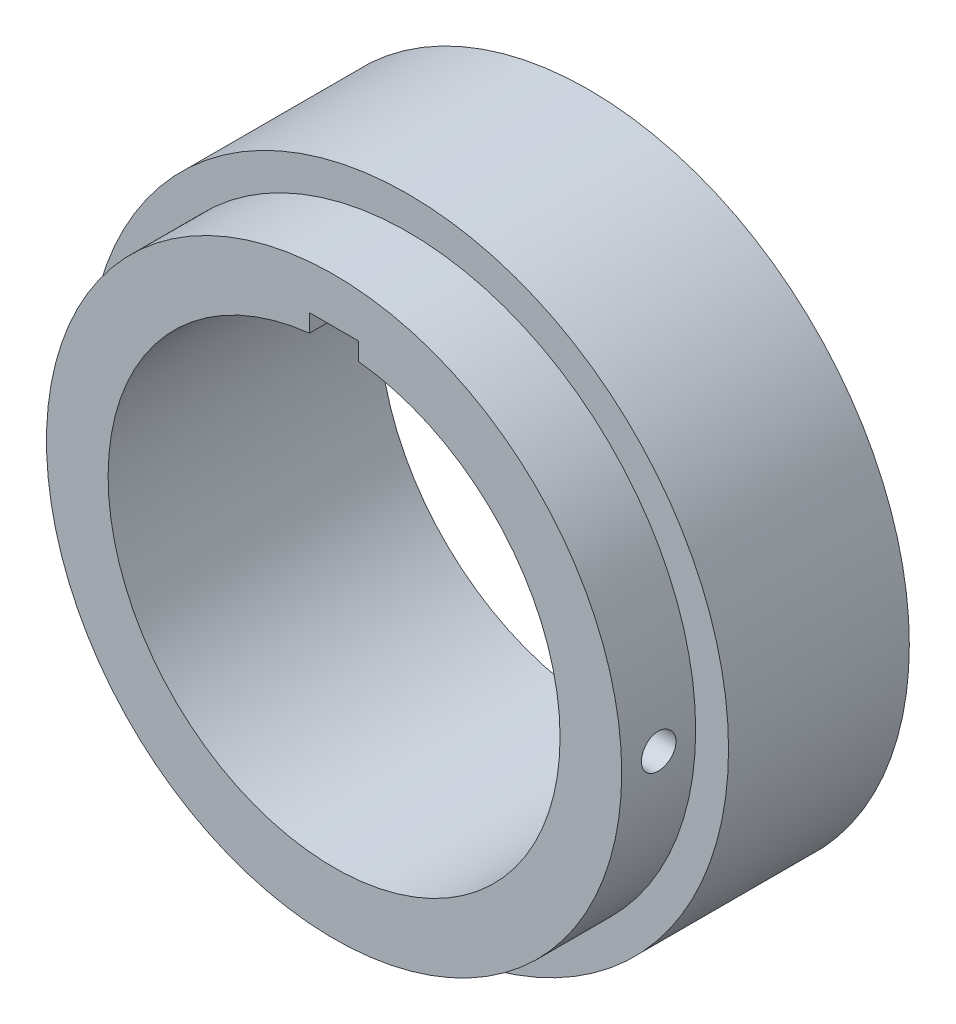
SolidWorks part; units mm, degrees
material "1023 Carbon Steel Sheet (SS)"
ref_plane "Front Plane" through (0, 0, 0) normal (0, 0, 1) x (1, 0, 0)
ref_plane "Top Plane" through (0, 0, 0) normal (0, 1, 0) x (1, 0, 0)
ref_plane "Right Plane" through (0, 0, 0) normal (1, 0, 0) x (0, 0, -1)
sketch "Sketch1" plane through (0, 0, 0) normal (0, 0, 1) x (1, 0, 0)
  circle A0 centre (0, 0) radius 39
  dimension "D1" = 78
extrude "Extrude1" add sketch "Sketch1" along normal blind 22
sketch "Sketch2" plane through (0, 0, 22) normal (0, 0, 1) x (1, 0, 0)
  circle A0 centre (0, 0) radius 35
  dimension "D1" = 70
extrude "Extrude2" add sketch "Sketch2" along normal blind 9
sketch "Sketch4" plane through (0, 0, 0) normal (0, 0, -1) x (-1, 0, 0)
  circle A0 centre (0, 0) radius 37.5
  dimension "D1" = 75
extrude "Extrude4" add sketch "Sketch4" along normal blind 2
sketch "Sketch3" plane through (0, 0, 31) normal (0, 0, 1) x (1, 0, 0)
  line L0 (0, 29.5) -> (0, 0) construction
  line L1 (-3, 29.5) -> (3, 29.5)
  line L2 (-3, 29.5) -> (-3, 27.3359)
  line L4 (3, 29.5) -> (3, 27.3359)
  arc A0 (-3, 27.3359) -> (3, 27.3359) centre (0, 0) ccw
  dimension "D1" = 55
  dimension "D2" = 6
  dimension "D3" = 2
extrude "Extrude3" cut sketch "Sketch3" against normal blind 113
chamfer "Chamfer1" distance 2 angle 45 1 edges at (-37.5, 0, -2)
ref_plane "Plane1" through (35, 0, 0) normal (1, 0, 0) x (0, 0, -1)
hole_wizard "M5 Tapped Hole6" positions "3DSketch3" profile "Sketch7" tap size "M5" standard "ISO"
sketch3d "3DSketch3"
  line L0 (0, 0, -10.2175) -> (0, 0, 26.5) construction
  point P0 (35, 0, 26.5)
  dimension "D1" = 4.5
sketch "Sketch7" plane through (35, 0, 26.5) normal (0, 1, 0) x (0, 0, -1)
  line L0 (0, 0) -> (0, 25.2618)
  line L1 (0, 25.2618) -> (2.1, 24)
  line L2 (2.1, 24) -> (2.1, 0)
  line L5 (2.1, 0) -> (0, 0)
  line L10 (0, 25.2618) -> (-2.1, 24) construction
  line L11 (0, -6.35) -> (0, 107.95) construction
  dimension "Tap Drill Dia." = 4.2
  dimension "Tap Drill Depth" = 24
  dimension "Drill Angle" = 118
cosmetic thread "Hole Thread1" parameters "D1"=7.5803, "D2"=5
